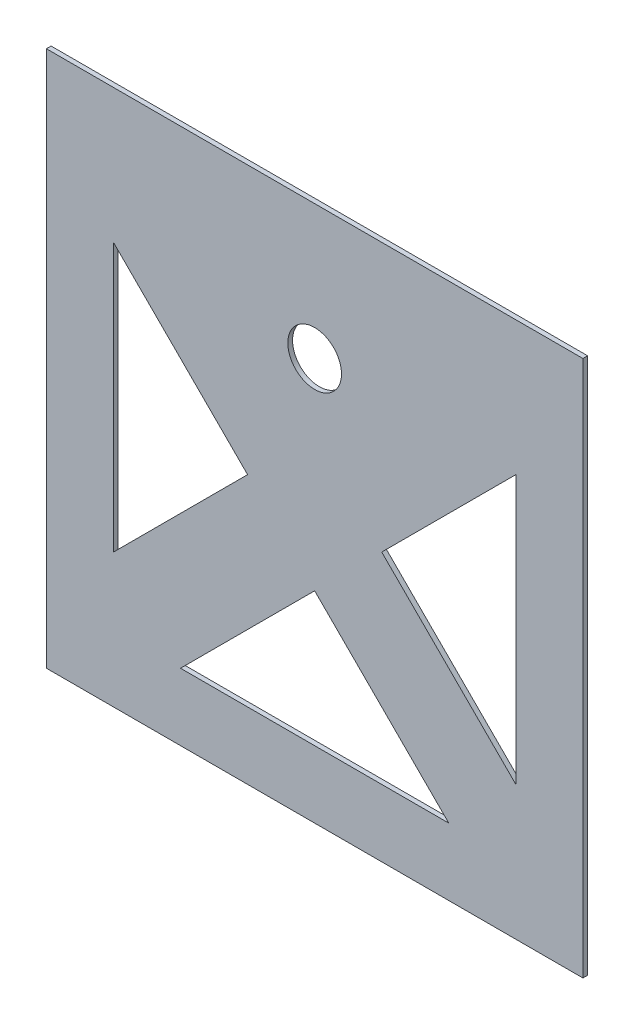
SolidWorks part; units mm, degrees
material "3.0205 (EN-AW 1200)"
ref_plane "Piano frontale" through (0, 0, 0) normal (0, 0, 1) x (1, 0, 0)
ref_plane "Piano superiore" through (0, 0, 0) normal (0, 1, 0) x (1, 0, 0)
ref_plane "Piano destro" through (0, 0, 0) normal (1, 0, 0) x (0, 0, -1)
sketch "Schizzo1" plane through (0, 0, 0) normal (0, 0, 1) x (1, 0, 0)
  line L1 (-400, 400) -> (400, 400)
  line L2 (-400, 400) -> (-400, -400)
  line L3 (-400, -400) -> (400, -400)
  line L4 (400, 400) -> (400, -400)
  line L5 (-400, 400) -> (400, -400) construction
  line L6 (-400, -400) -> (400, 400) construction
  point P0 (0, 0)
  dimension "D1" = 800
  dimension "D2" = 800
extrude "Estrusione-Estrusione1" add sketch "Schizzo1" along normal blind 7
sketch "Schizzo2" plane through (0, 0, 7) normal (0, 0, 1) x (1, 0, 0)
  circle A0 centre (0, 200) radius 40
  dimension "D2" = 80
  dimension "D1" = 200
extrude "Taglio-Estrusione1" cut sketch "Schizzo2" against normal blind 15
sketch "Schizzo3" plane through (0, 0, 7) normal (0, 0, 1) x (1, 0, 0)
  line L0 (-400, 400) -> (400, -400) construction
  line L1 (-400, 0) -> (400, 0) construction
  line L2 (400, 400) -> (-400, -400) construction
  line L3 (-400, 400) -> (-400, -400) construction
  line L4 (400, -400) -> (400, 400) construction
  line L5 (-300, 200) -> (-300, -200)
  line L6 (400, 400) -> (-400, 400) construction
  line L7 (0, 400) -> (0, -400) construction
  line L8 (-400, -400) -> (400, -400) construction
  line L9 (-300, -200) -> (-100, 0)
  line L10 (-100, 0) -> (-300, 200)
  line L11 (300, -200) -> (300, 200)
  line L12 (300, 200) -> (100, 0)
  line L13 (100, 0) -> (300, -200)
  line L14 (200, -300) -> (0, -100)
  line L15 (0, -100) -> (-200, -300)
  line L16 (-200, -300) -> (200, -300)
  point P28 (-300, 0)
  point P30 (300, 0)
  point P31 (0, -300)
  dimension "D1" = 100
  dimension "D2" = 100
  dimension "D3" = 100
  dimension "D4" = 100
  dimension "D5" = 100
  dimension "D6" = 100
extrude "Taglio-Estrusione2" cut sketch "Schizzo3" against normal through all
